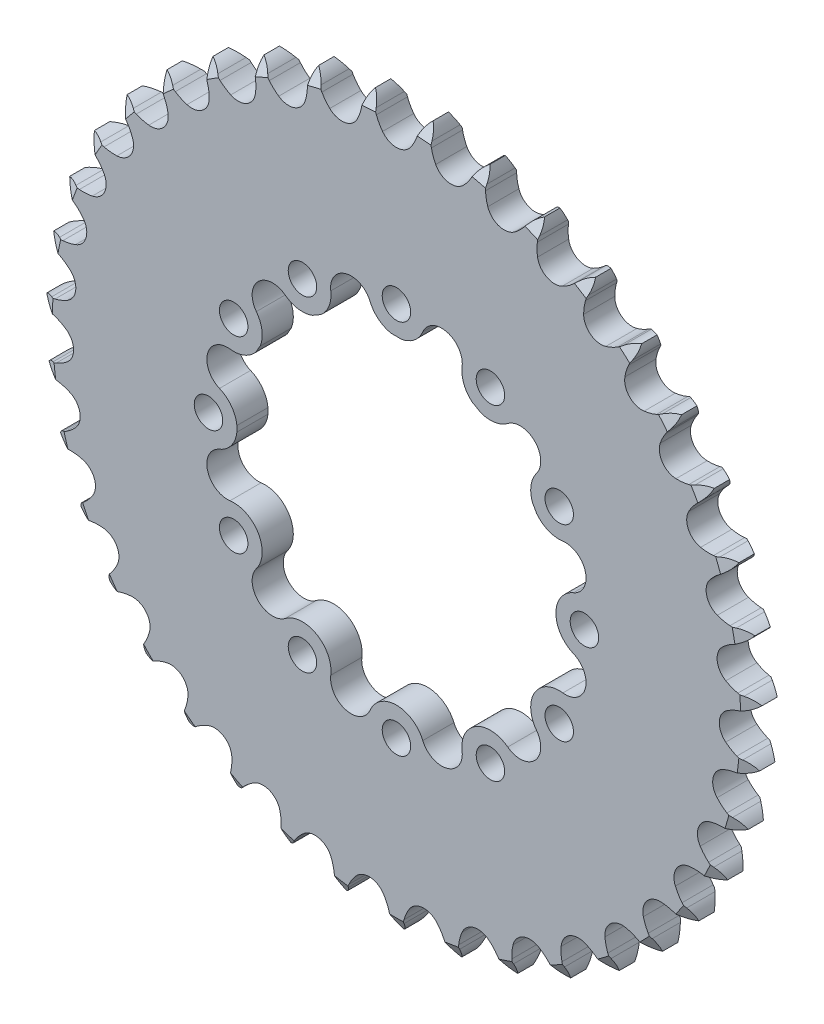
SolidWorks part; units mm, degrees
material "7075-T6 (SN)"
ref_plane "Front Plane" through (0, 0, 0) normal (0, 0, 1) x (1, 0, 0)
ref_plane "Top Plane" through (0, 0, 0) normal (0, 1, 0) x (1, 0, 0)
ref_plane "Right Plane" through (0, 0, 0) normal (1, 0, 0) x (0, 0, -1)
sketch "Work Sketch" plane through (0, 0, 0) normal (0, 0, 1) x (1, 0, 0)
  line L0 (0, 0) -> (0, 160.4542) construction
  line L1 (-112.0919, 78.9148) -> (87.2579, 78.9148) construction
  line L2 (5.102, 120.8822) -> (5.102, 112.9699) construction
  line L3 (-12.8497, 82.6953) -> (16.7256, 82.6953) construction
  line L4 (5.102, 82.6953) -> (-6.0879, 74.4036) construction
  line L5 (5.102, 82.6953) -> (-4.6505, 79.1506) construction
  line L6 (-4.6505, 79.1506) -> (-6.8863, 85.3019)
  line L7 (-11.5114, 78.0206) -> (-7.1525, 78.0206) construction
  line L8 (-11.0765, 124.7602) -> (-11.0765, 110.2345) construction
  line L9 (0, 0) -> (-3.4402, 42.6146) construction
  circle A0 centre (0, 0) radius 78.9148
  circle A1 centre (0, 78.9148) radius 4.0088
  arc A2 (-4.6505, 79.1506) -> (-3.2209, 76.5281) centre (5.0804, 82.7541) ccw
  circle A3 centre (-11.0765, 78.0206) radius 6.4254
  point P23 (-3.2209, 76.5281)
  dimension "D1" = 157.8295
  dimension "D8" = 10.3767
  dimension "D2" = 8.0177
  dimension "D3" = 5.102
  dimension "D4" = 3.7806
  dimension "D5" = 36.538
  dimension "D6" = 16.564
  dimension "D7" = 10.3767
  dimension "D9" = 0.8942
  dimension "D10" = 11.0765
  dimension "D11" = 4.615
sketch "Teeth Sketch" plane through (0, 0, 0) normal (0, 0, 1) x (1, 0, 0)
  line L0 (5.0376, 80.2155) -> (4.6505, 79.1506)
  line L1 (-7.4865, 92.7372) -> (-4.7839, 59.2593) construction
  line L2 (0, 0) -> (-10.9133, 132.3061) construction
  line L3 (7.8951, 79.9848) -> (8.1063, 78.8717)
  line L4 (16093.3137, -199351.4616) -> (-16096.7539, 199394.0762) construction
  line L5 (0, 146.3285) -> (0, 56.9858) construction
  line L6 (17.8398, 78.3686) -> (17.287, 77.3797)
  line L7 (0, -200000) -> (0, 200160.4542) construction
  line L8 (20.6234, 77.6826) -> (20.6533, 76.5499)
  line L9 (-4.6505, 79.1506) -> (-6.8863, 85.3019) construction
  line L10 (44.1616, 67.154) -> (43.8313, 66.0702)
  line L11 (-5.0376, 80.2155) -> (-4.6505, 79.1506)
  line L12 (30.18, 74.4921) -> (29.4757, 73.6046)
  line L13 (32.8175, 73.3684) -> (32.6653, 72.2456)
  line L14 (41.7385, 68.6862) -> (40.901, 67.9232)
  line L15 (52.2161, 61.1014) -> (51.267, 60.4826)
  line L16 (54.362, 59.2003) -> (53.8621, 58.1836)
  line L17 (61.3413, 51.9341) -> (60.3052, 51.4756)
  line L18 (63.1544, 49.7134) -> (62.4979, 48.79)
  line L19 (68.8777, 41.4218) -> (67.7815, 41.1354)
  line L20 (70.3112, 38.939) -> (69.515, 38.1328)
  line L21 (74.6303, 29.8366) -> (73.5023, 29.7298)
  line L22 (75.6469, 27.156) -> (74.7318, 26.488)
  line L23 (78.45, 17.4787) -> (77.3195, 17.5542)
  line L24 (79.0234, 14.6698) -> (78.013, 14.1572)
  line L25 (80.2378, 4.6681) -> (79.1341, 4.9239)
  line L26 (80.3533, 1.8035) -> (79.2737, 1.4597)
  line L27 (79.9476, -8.2634) -> (78.8992, -7.8338)
  line L28 (79.602, -11.1094) -> (78.4813, -11.2756)
  line L29 (77.5867, -20.9809) -> (76.6208, -20.3887)
  line L30 (76.7891, -23.7346) -> (75.6562, -23.7189)
  line L31 (73.2164, -33.155) -> (72.358, -32.4155)
  line L32 (71.9874, -35.7451) -> (70.8717, -35.5478)
  line L33 (66.9499, -44.4704) -> (66.2212, -43.6028)
  line L34 (65.3213, -46.8298) -> (64.2517, -46.4561)
  line L35 (58.9493, -54.634) -> (58.3693, -53.6608)
  line L36 (56.9634, -56.7016) -> (55.9676, -56.1612)
  line L37 (49.422, -63.3827) -> (49.0056, -62.329)
  line L38 (47.1301, -65.1049) -> (46.2339, -64.4118)
  line L39 (38.6147, -70.4897) -> (38.3727, -69.3829)
  line L40 (36.0763, -71.822) -> (35.3028, -70.9941)
  line L41 (26.8073, -75.7712) -> (26.746, -74.6398)
  line L42 (24.088, -76.679) -> (23.4574, -75.7377)
  line L43 (14.3056, -79.0901) -> (14.4266, -77.9636)
  line L44 (11.4759, -79.55) -> (11.0044, -78.5198)
  line L45 (1.4334, -80.3607) -> (1.7335, -79.2682)
  line L46 (-1.4334, -80.3607) -> (-1.7335, -79.2682)
  line L47 (-11.4759, -79.55) -> (-11.0044, -78.5198)
  line L48 (-14.3056, -79.0901) -> (-14.4266, -77.9636)
  line L49 (-24.088, -76.679) -> (-23.4574, -75.7377)
  line L50 (-26.8073, -75.7712) -> (-26.746, -74.6398)
  line L51 (-36.0763, -71.822) -> (-35.3028, -70.9941)
  line L52 (-38.6147, -70.4897) -> (-38.3727, -69.3829)
  line L53 (-47.1301, -65.1049) -> (-46.2339, -64.4118)
  line L54 (-49.422, -63.3827) -> (-49.0056, -62.329)
  line L55 (-56.9634, -56.7016) -> (-55.9676, -56.1612)
  line L56 (-58.9493, -54.634) -> (-58.3693, -53.6608)
  line L57 (-65.3213, -46.8298) -> (-64.2517, -46.4561)
  line L58 (-66.9499, -44.4704) -> (-66.2212, -43.6028)
  line L59 (-71.9874, -35.7451) -> (-70.8717, -35.5478)
  line L60 (-73.2164, -33.155) -> (-72.358, -32.4155)
  line L61 (-76.7891, -23.7346) -> (-75.6562, -23.7189)
  line L62 (-77.5867, -20.9809) -> (-76.6208, -20.3887)
  line L63 (-79.602, -11.1094) -> (-78.4813, -11.2756)
  line L64 (-79.9476, -8.2634) -> (-78.8992, -7.8338)
  line L65 (-80.3533, 1.8035) -> (-79.2737, 1.4597)
  line L66 (-80.2378, 4.6681) -> (-79.1341, 4.9239)
  line L67 (-79.0234, 14.6698) -> (-78.013, 14.1572)
  line L68 (-78.45, 17.4787) -> (-77.3195, 17.5542)
  line L69 (-75.6469, 27.156) -> (-74.7318, 26.488)
  line L70 (-74.6303, 29.8366) -> (-73.5023, 29.7298)
  line L71 (-70.3112, 38.939) -> (-69.515, 38.1328)
  line L72 (-68.8777, 41.4218) -> (-67.7815, 41.1354)
  line L73 (-63.1544, 49.7134) -> (-62.4979, 48.79)
  line L74 (-61.3413, 51.9341) -> (-60.3052, 51.4756)
  line L75 (-54.362, 59.2003) -> (-53.8621, 58.1836)
  line L76 (-52.2161, 61.1014) -> (-51.267, 60.4826)
  line L77 (-44.1616, 67.154) -> (-43.8313, 66.0702)
  line L78 (-41.7385, 68.6862) -> (-40.901, 67.9232)
  line L79 (-32.8175, 73.3684) -> (-32.6653, 72.2456)
  line L80 (-30.18, 74.4921) -> (-29.4757, 73.6046)
  line L81 (-20.6234, 77.6826) -> (-20.6533, 76.5499)
  line L82 (-17.8398, 78.3686) -> (-17.287, 77.3797)
  line L83 (-7.8951, 79.9848) -> (-8.1063, 78.8717)
  arc A0 (-6.8336, 82.8459) -> (-5.0376, 80.2155) centre (-11.0765, 78.0206) cw
  circle A1 centre (-11.0765, 78.0206) radius 6.4254 construction
  arc A2 (-3.2209, 76.5281) -> (-4.6505, 79.1506) centre (5.0804, 82.7541) cw
  arc A3 (-4.6505, 79.1506) -> (-3.2209, 76.5281) centre (5.0804, 82.7541) ccw construction
  circle A4 centre (0, 78.9148) radius 4.0088 construction
  arc A5 (-3.2209, 76.5281) -> (3.2209, 76.5281) centre (0, 78.9148) ccw
  arc A6 (3.2209, 76.5281) -> (4.6505, 79.1506) centre (-5.0804, 82.7541) ccw
  arc A7 (6.8336, 82.8459) -> (5.0376, 80.2155) centre (11.0765, 78.0206) ccw
  arc A8 (6.5443, 82.8692) -> (7.8951, 79.9848) centre (1.5824, 78.787) cw
  arc A9 (9.0967, 76.0537) -> (8.1063, 78.8717) centre (18.2893, 80.8676) cw
  arc A10 (9.0967, 76.0537) -> (15.4552, 75.0204) centre (12.6588, 77.8928) ccw
  arc A11 (15.4552, 75.0204) -> (17.287, 77.3797) centre (8.2601, 82.4975) ccw
  arc A12 (20.0345, 80.6769) -> (17.8398, 78.3686) centre (23.4484, 75.2334) ccw
  arc A13 (19.7528, 80.7463) -> (20.6234, 77.6826) centre (14.2002, 77.5129) cw
  arc A14 (21.1788, 73.6096) -> (20.6533, 76.5499) centre (31.0245, 76.8865) cw
  arc A15 (21.1788, 73.6096) -> (27.2892, 71.5697) centre (24.9898, 74.8535) ccw
  arc A16 (27.2892, 71.5697) -> (29.4757, 73.6046) centre (21.3867, 80.1041) ccw
  arc A17 (32.7165, 76.4184) -> (30.18, 74.4921) centre (35.2131, 70.4978) ccw
  arc A18 (32.4496, 76.5321) -> (32.8175, 73.3684) centre (26.4502, 74.2313) cw
  arc A19 (32.7124, 69.2591) -> (32.6653, 72.2456) centre (42.9562, 70.9142) cw
  arc A20 (32.7124, 69.2591) -> (38.4163, 66.2654) centre (36.6735, 69.8756) ccw
  arc A21 (38.4163, 66.2654) -> (40.901, 67.9232) centre (33.9593, 75.6361) ccw
  arc A22 (44.5512, 70.1807) -> (41.7385, 68.6862) centre (46.0657, 63.9363) ccw
  arc A23 (44.306, 70.3358) -> (44.1616, 67.154) centre (38.0153, 69.0271) cw
  arc A24 (43.3987, 63.1147) -> (43.8313, 66.0702) centre (53.7754, 63.1052) cw
  arc A25 (43.3987, 63.1147) -> (48.5486, 59.2448) centre (47.4074, 63.0878) ccw
  arc A26 (48.5486, 59.2448) -> (51.267, 60.4826) centre (45.6524, 69.2092) ccw
  arc A27 (55.2321, 62.1253) -> (52.2161, 61.1014) centre (55.7253, 55.7189) ccw
  arc A28 (55.0149, 62.3178) -> (54.362, 59.2003) centre (48.5957, 62.0351) cw
  arc A29 (52.961, 55.3358) -> (53.8621, 58.1836) centre (63.2018, 53.6618) cw
  arc A30 (52.961, 55.3358) -> (57.4234, 50.6899) centre (56.9135, 54.6662) ccw
  arc A31 (57.4234, 50.6899) -> (60.3052, 51.4756) centre (56.1632, 60.9898) ccw
  arc A32 (64.4824, 52.461) -> (61.3413, 51.9341) centre (63.9416, 46.0584) ccw
  arc A33 (64.2989, 52.6858) -> (63.1544, 49.7134) centre (57.9175, 53.4365) cw
  arc A34 (61.1517, 46.1237) -> (62.4979, 48.79) centre (70.9913, 42.8287) cw
  arc A35 (61.1517, 46.1237) -> (64.811, 40.8221) centre (64.9456, 44.8287) ccw
  arc A36 (64.811, 40.8221) -> (67.7815, 41.1354) centre (65.2193, 51.1908) ccw
  arc A37 (72.0627, 41.4379) -> (68.8777, 41.4218) centre (70.5018, 35.205) ccw
  arc A38 (71.9177, 41.6892) -> (70.3112, 38.939) centre (65.7393, 43.4539) cw
  arc A39 (67.7585, 35.717) -> (69.515, 38.1328) centre (76.9422, 30.8862) cw
  arc A40 (67.7585, 35.717) -> (70.5201, 29.8971) centre (71.2956, 33.8302) ccw
  arc A41 (70.5201, 29.8971) -> (73.5023, 29.7298) centre (72.5864, 40.0659) ccw
  arc A42 (77.7767, 29.3416) -> (74.6303, 29.8366) centre (75.2361, 23.4398) ccw
  arc A43 (77.6738, 29.6129) -> (75.6469, 27.156) centre (71.8585, 32.3458) cw
  arc A44 (72.6105, 24.3852) -> (74.7318, 26.488) centre (80.9003, 18.1439) cw
  arc A45 (72.6105, 24.3852) -> (74.4027, 18.1977) centre (75.7991, 21.9555) ccw
  arc A46 (74.4027, 18.1977) -> (77.3195, 17.5542) centre (78.0734, 27.9034) ccw
  arc A47 (81.4762, 16.4854) -> (78.45, 17.4787) centre (78.0218, 11.0675) ccw
  arc A48 (81.4182, 16.7697) -> (79.0234, 14.6698) centre (76.1166, 20.4) cw
  arc A49 (75.5818, 12.4219) -> (78.013, 14.1572) centre (82.7631, 4.9316) cw
  arc A50 (75.5818, 12.4219) -> (76.3583, 6.027) centre (78.3394, 9.5121) ccw
  arc A51 (76.3583, 6.027) -> (79.1341, 4.9239) centre (81.5384, 15.0182) ccw
  arc A52 (83.0656, 3.2022) -> (80.2378, 4.6681) centre (78.7868, -1.5914) ccw
  arc A53 (83.0539, 3.4922) -> (80.3533, 1.8035) centre (78.4033, 7.9259) cw
  arc A54 (76.5957, 0.1368) -> (79.2737, 1.4597) centre (82.4825, -8.4084) cw
  arc A55 (76.5957, 0.1368) -> (76.3363, -6.2998) centre (78.8508, -3.1776) ccw
  arc A56 (76.3363, -6.2998) -> (78.8992, -7.8338) centre (82.8916, 1.7441) ccw
  arc A57 (82.5035, -10.1639) -> (79.9476, -8.2634) centre (77.5113, -14.2091) ccw
  arc A58 (82.5385, -9.8758) -> (79.602, -11.1094) centre (78.6594, -4.7535) cw
  arc A59 (75.6257, -12.1517) -> (78.4813, -11.2756) centre (80.0655, -21.5307) cw
  arc A60 (75.6257, -12.1517) -> (74.3372, -18.4634) centre (77.3199, -15.785) ccw
  arc A61 (74.3372, -18.4634) -> (76.6208, -20.3887) centre (82.0979, -11.5753) ccw
  arc A62 (79.8047, -23.2668) -> (77.5867, -20.9809) centre (74.2283, -26.4587) ccw
  arc A63 (79.8855, -22.9881) -> (76.7891, -23.7346) centre (76.8783, -17.3098) cw
  arc A64 (72.6971, -24.1256) -> (75.6562, -23.7189) centre (75.5749, -34.0953) cw
  arc A65 (72.6971, -24.1256) -> (70.4128, -30.1488) centre (73.7866, -27.9836) ccw
  arc A66 (70.4128, -30.1488) -> (72.358, -32.4155) centre (79.178, -24.5948) ccw
  arc A67 (75.039, -35.7671) -> (73.2164, -33.155) centre (69.0227, -38.0232) ccw
  arc A68 (75.1634, -35.5049) -> (71.9874, -35.7451) centre (73.106, -29.4178) cw
  arc A69 (67.8857, -35.4746) -> (70.8717, -35.5478) centre (69.127, -45.7768) cw
  arc A70 (67.8857, -35.4746) -> (64.6648, -41.0534) centre (68.3422, -39.4574) ccw
  arc A71 (64.6648, -41.0534) -> (66.2212, -43.6028) centre (74.2074, -36.9773) ccw
  arc A72 (68.3299, -47.341) -> (66.9499, -44.4704) centre (62.0296, -48.6028) ccw
  arc A73 (68.4947, -47.1022) -> (65.3213, -46.8298) centre (67.4404, -40.7639) cw
  arc A74 (61.3161, -45.9049) -> (64.2517, -46.4561) centre (60.8887, -56.2728) cw
  arc A75 (61.3161, -45.9049) -> (57.2419, -50.8948) centre (61.1278, -49.9093) ccw
  arc A76 (57.2419, -50.8948) -> (58.3693, -53.6608) centre (67.3148, -48.4022) ccw
  arc A77 (59.851, -57.6888) -> (58.9493, -54.634) centre (53.4299, -57.9236) ccw
  arc A78 (60.052, -57.4796) -> (56.9634, -56.7016) centre (60.0281, -51.0542) cw
  arc A79 (53.1584, -55.1462) -> (55.9676, -56.1612) centre (51.0734, -65.3113) cw
  arc A80 (53.1584, -55.1462) -> (48.3366, -59.4179) centre (52.3302, -59.0685) ccw
  arc A81 (48.3366, -59.4179) -> (49.0056, -62.329) centre (58.6789, -58.5735) ccw
  arc A82 (49.822, -66.5425) -> (49.422, -63.3827) centre (43.4464, -65.7443) ccw
  arc A83 (50.054, -66.3682) -> (47.1301, -65.1049) centre (51.0611, -60.0222) cw
  arc A84 (43.6239, -62.9593) -> (46.2339, -64.4118) centre (39.9354, -72.6583) cw
  arc A85 (43.6239, -62.9593) -> (38.1793, -66.4022) centre (42.1772, -66.698) ccw
  arc A86 (38.1793, -66.4022) -> (38.3727, -69.3829) centre (48.5231, -67.2277) ccw
  arc A87 (38.5026, -73.6728) -> (38.6147, -70.4897) centre (32.3376, -71.8622) ccw
  arc A88 (38.7596, -73.538) -> (36.0763, -71.822) centre (40.7716, -67.4357) cw
  arc A89 (32.9596, -69.1417) -> (35.3028, -70.9941) centre (27.763, -78.1234) cw
  arc A90 (32.9596, -69.1417) -> (27.0333, -71.6667) centre (30.932, -72.6) ccw
  arc A91 (27.0333, -71.6667) -> (26.746, -74.6398) centre (37.1107, -74.1408) ccw
  arc A92 (26.1861, -78.8951) -> (26.8073, -75.7712) centre (20.3913, -76.1189) ccw
  arc A93 (26.4613, -78.8032) -> (24.088, -76.679) centre (29.4261, -73.1027) cw
  arc A94 (21.4417, -73.5335) -> (23.4574, -75.7377) centre (14.8716, -81.5653) cw
  arc A95 (21.4417, -73.5335) -> (15.187, -75.0751) centre (18.8855, -76.6216) ccw
  arc A96 (15.187, -75.0751) -> (14.4266, -77.9636) centre (24.7371, -79.1336) ccw
  arc A97 (13.1913, -82.0739) -> (14.3056, -79.0901) centre (7.9169, -78.4042) ccw
  arc A98 (13.4777, -82.0274) -> (11.4759, -79.55) centre (17.3186, -76.8763) cw
  arc A99 (9.3684, -76.0207) -> (11.0044, -78.5198) centre (1.595, -82.8946) cw
  arc A100 (9.3684, -76.0207) -> (2.9475, -76.5391) centre (6.35, -78.6589) ccw
  arc A101 (2.9475, -76.5391) -> (1.7335, -79.2682) centre (11.7228, -82.077) ccw
  arc A102 (-0.1451, -83.1271) -> (1.4334, -80.3607) centre (-4.7625, -78.6589) ccw
  arc A103 (0.1451, -83.1271) -> (-1.4334, -80.3607) centre (4.7625, -78.6589) cw
  arc A104 (-2.9475, -76.5391) -> (-1.7335, -79.2682) centre (-11.7228, -82.077) cw
  arc A105 (-2.9475, -76.5391) -> (-9.3684, -76.0207) centre (-6.35, -78.6589) ccw
  arc A106 (-9.3684, -76.0207) -> (-11.0044, -78.5198) centre (-1.595, -82.8946) ccw
  arc A107 (-13.4777, -82.0274) -> (-11.4759, -79.55) centre (-17.3186, -76.8763) ccw
  arc A108 (-13.1913, -82.0739) -> (-14.3056, -79.0901) centre (-7.9169, -78.4042) cw
  arc A109 (-15.187, -75.0751) -> (-14.4266, -77.9636) centre (-24.7371, -79.1336) cw
  arc A110 (-15.187, -75.0751) -> (-21.4417, -73.5335) centre (-18.8855, -76.6216) ccw
  arc A111 (-21.4417, -73.5335) -> (-23.4574, -75.7377) centre (-14.8716, -81.5653) ccw
  arc A112 (-26.4613, -78.8032) -> (-24.088, -76.679) centre (-29.4261, -73.1027) ccw
  arc A113 (-26.1861, -78.8951) -> (-26.8073, -75.7712) centre (-20.3913, -76.1189) cw
  arc A114 (-27.0333, -71.6667) -> (-26.746, -74.6398) centre (-37.1107, -74.1408) cw
  arc A115 (-27.0333, -71.6667) -> (-32.9596, -69.1417) centre (-30.932, -72.6) ccw
  arc A116 (-32.9596, -69.1417) -> (-35.3028, -70.9941) centre (-27.763, -78.1234) ccw
  arc A117 (-38.7596, -73.538) -> (-36.0763, -71.822) centre (-40.7716, -67.4357) ccw
  arc A118 (-38.5026, -73.6728) -> (-38.6147, -70.4897) centre (-32.3376, -71.8622) cw
  arc A119 (-38.1793, -66.4022) -> (-38.3727, -69.3829) centre (-48.5231, -67.2277) cw
  arc A120 (-38.1793, -66.4022) -> (-43.6239, -62.9593) centre (-42.1772, -66.698) ccw
  arc A121 (-43.6239, -62.9593) -> (-46.2339, -64.4118) centre (-39.9354, -72.6583) ccw
  arc A122 (-50.054, -66.3682) -> (-47.1301, -65.1049) centre (-51.0611, -60.0222) ccw
  arc A123 (-49.822, -66.5425) -> (-49.422, -63.3827) centre (-43.4464, -65.7443) cw
  arc A124 (-48.3366, -59.4179) -> (-49.0056, -62.329) centre (-58.6789, -58.5735) cw
  arc A125 (-48.3366, -59.4179) -> (-53.1584, -55.1462) centre (-52.3302, -59.0685) ccw
  arc A126 (-53.1584, -55.1462) -> (-55.9676, -56.1612) centre (-51.0734, -65.3113) ccw
  arc A127 (-60.052, -57.4796) -> (-56.9634, -56.7016) centre (-60.0281, -51.0542) ccw
  arc A128 (-59.851, -57.6888) -> (-58.9493, -54.634) centre (-53.4299, -57.9236) cw
  arc A129 (-57.2419, -50.8948) -> (-58.3693, -53.6608) centre (-67.3148, -48.4022) cw
  arc A130 (-57.2419, -50.8948) -> (-61.3161, -45.9049) centre (-61.1278, -49.9093) ccw
  arc A131 (-61.3161, -45.9049) -> (-64.2517, -46.4561) centre (-60.8887, -56.2728) ccw
  arc A132 (-68.4947, -47.1022) -> (-65.3213, -46.8298) centre (-67.4404, -40.7639) ccw
  arc A133 (-68.3299, -47.341) -> (-66.9499, -44.4704) centre (-62.0296, -48.6028) cw
  arc A134 (-64.6648, -41.0534) -> (-66.2212, -43.6028) centre (-74.2074, -36.9773) cw
  arc A135 (-64.6648, -41.0534) -> (-67.8857, -35.4746) centre (-68.3422, -39.4574) ccw
  arc A136 (-67.8857, -35.4746) -> (-70.8717, -35.5478) centre (-69.127, -45.7768) ccw
  arc A137 (-75.1634, -35.5049) -> (-71.9874, -35.7451) centre (-73.106, -29.4178) ccw
  arc A138 (-75.039, -35.7671) -> (-73.2164, -33.155) centre (-69.0227, -38.0232) cw
  arc A139 (-70.4128, -30.1488) -> (-72.358, -32.4155) centre (-79.178, -24.5948) cw
  arc A140 (-70.4128, -30.1488) -> (-72.6971, -24.1256) centre (-73.7866, -27.9836) ccw
  arc A141 (-72.6971, -24.1256) -> (-75.6562, -23.7189) centre (-75.5749, -34.0953) ccw
  arc A142 (-79.8855, -22.9881) -> (-76.7891, -23.7346) centre (-76.8783, -17.3098) ccw
  arc A143 (-79.8047, -23.2668) -> (-77.5867, -20.9809) centre (-74.2283, -26.4587) cw
  arc A144 (-74.3372, -18.4634) -> (-76.6208, -20.3887) centre (-82.0979, -11.5753) cw
  arc A145 (-74.3372, -18.4634) -> (-75.6257, -12.1517) centre (-77.3199, -15.785) ccw
  arc A146 (-75.6257, -12.1517) -> (-78.4813, -11.2756) centre (-80.0655, -21.5307) ccw
  arc A147 (-82.5385, -9.8758) -> (-79.602, -11.1094) centre (-78.6594, -4.7535) ccw
  arc A148 (-82.5035, -10.1639) -> (-79.9476, -8.2634) centre (-77.5113, -14.2091) cw
  arc A149 (-76.3363, -6.2998) -> (-78.8992, -7.8338) centre (-82.8916, 1.7441) cw
  arc A150 (-76.3363, -6.2998) -> (-76.5957, 0.1368) centre (-78.8508, -3.1776) ccw
  arc A151 (-76.5957, 0.1368) -> (-79.2737, 1.4597) centre (-82.4825, -8.4084) ccw
  arc A152 (-83.0539, 3.4922) -> (-80.3533, 1.8035) centre (-78.4033, 7.9259) ccw
  arc A153 (-83.0656, 3.2022) -> (-80.2378, 4.6681) centre (-78.7868, -1.5914) cw
  arc A154 (-76.3583, 6.027) -> (-79.1341, 4.9239) centre (-81.5384, 15.0182) cw
  arc A155 (-76.3583, 6.027) -> (-75.5818, 12.4219) centre (-78.3394, 9.5121) ccw
  arc A156 (-75.5818, 12.4219) -> (-78.013, 14.1572) centre (-82.7631, 4.9316) ccw
  arc A157 (-81.4182, 16.7697) -> (-79.0234, 14.6698) centre (-76.1166, 20.4) ccw
  arc A158 (-81.4762, 16.4854) -> (-78.45, 17.4787) centre (-78.0218, 11.0675) cw
  arc A159 (-74.4027, 18.1977) -> (-77.3195, 17.5542) centre (-78.0734, 27.9034) cw
  arc A160 (-74.4027, 18.1977) -> (-72.6105, 24.3852) centre (-75.7991, 21.9555) ccw
  arc A161 (-72.6105, 24.3852) -> (-74.7318, 26.488) centre (-80.9003, 18.1439) ccw
  arc A162 (-77.6738, 29.6129) -> (-75.6469, 27.156) centre (-71.8585, 32.3458) ccw
  arc A163 (-77.7767, 29.3416) -> (-74.6303, 29.8366) centre (-75.2361, 23.4398) cw
  arc A164 (-70.5201, 29.8971) -> (-73.5023, 29.7298) centre (-72.5864, 40.0659) cw
  arc A165 (-70.5201, 29.8971) -> (-67.7585, 35.717) centre (-71.2956, 33.8302) ccw
  arc A166 (-67.7585, 35.717) -> (-69.515, 38.1328) centre (-76.9422, 30.8862) ccw
  arc A167 (-71.9177, 41.6892) -> (-70.3112, 38.939) centre (-65.7393, 43.4539) ccw
  arc A168 (-72.0627, 41.4379) -> (-68.8777, 41.4218) centre (-70.5018, 35.205) cw
  arc A169 (-64.811, 40.8221) -> (-67.7815, 41.1354) centre (-65.2193, 51.1908) cw
  arc A170 (-64.811, 40.8221) -> (-61.1517, 46.1237) centre (-64.9456, 44.8287) ccw
  arc A171 (-61.1517, 46.1237) -> (-62.4979, 48.79) centre (-70.9913, 42.8287) ccw
  arc A172 (-64.2989, 52.6858) -> (-63.1544, 49.7134) centre (-57.9175, 53.4365) ccw
  arc A173 (-64.4824, 52.461) -> (-61.3413, 51.9341) centre (-63.9416, 46.0584) cw
  arc A174 (-57.4234, 50.6899) -> (-60.3052, 51.4756) centre (-56.1632, 60.9898) cw
  arc A175 (-57.4234, 50.6899) -> (-52.961, 55.3358) centre (-56.9135, 54.6662) ccw
  arc A176 (-52.961, 55.3358) -> (-53.8621, 58.1836) centre (-63.2018, 53.6618) ccw
  arc A177 (-55.0149, 62.3178) -> (-54.362, 59.2003) centre (-48.5957, 62.0351) ccw
  arc A178 (-55.2321, 62.1253) -> (-52.2161, 61.1014) centre (-55.7253, 55.7189) cw
  arc A179 (-48.5486, 59.2448) -> (-51.267, 60.4826) centre (-45.6524, 69.2092) cw
  arc A180 (-48.5486, 59.2448) -> (-43.3987, 63.1147) centre (-47.4074, 63.0878) ccw
  arc A181 (-43.3987, 63.1147) -> (-43.8313, 66.0702) centre (-53.7754, 63.1052) ccw
  arc A182 (-44.306, 70.3358) -> (-44.1616, 67.154) centre (-38.0153, 69.0271) ccw
  arc A183 (-44.5512, 70.1807) -> (-41.7385, 68.6862) centre (-46.0657, 63.9363) cw
  arc A184 (-38.4163, 66.2654) -> (-40.901, 67.9232) centre (-33.9593, 75.6361) cw
  arc A185 (-38.4163, 66.2654) -> (-32.7124, 69.2591) centre (-36.6735, 69.8756) ccw
  arc A186 (-32.7124, 69.2591) -> (-32.6653, 72.2456) centre (-42.9562, 70.9142) ccw
  arc A187 (-32.4496, 76.5321) -> (-32.8175, 73.3684) centre (-26.4502, 74.2313) ccw
  arc A188 (-32.7165, 76.4184) -> (-30.18, 74.4921) centre (-35.2131, 70.4978) cw
  arc A189 (-27.2892, 71.5697) -> (-29.4757, 73.6046) centre (-21.3867, 80.1041) cw
  arc A190 (-27.2892, 71.5697) -> (-21.1788, 73.6096) centre (-24.9898, 74.8535) ccw
  arc A191 (-21.1788, 73.6096) -> (-20.6533, 76.5499) centre (-31.0245, 76.8865) ccw
  arc A192 (-19.7528, 80.7463) -> (-20.6234, 77.6826) centre (-14.2002, 77.5129) ccw
  arc A193 (-20.0345, 80.6769) -> (-17.8398, 78.3686) centre (-23.4484, 75.2334) cw
  arc A194 (-15.4552, 75.0204) -> (-17.287, 77.3797) centre (-8.2601, 82.4975) cw
  arc A195 (-15.4552, 75.0204) -> (-9.0967, 76.0537) centre (-12.6588, 77.8928) ccw
  arc A196 (-9.0967, 76.0537) -> (-8.1063, 78.8717) centre (-18.2893, 80.8676) ccw
  arc A197 (-6.5443, 82.8692) -> (-7.8951, 79.9848) centre (-1.5824, 78.787) ccw
  point P77 (0, 0)
  dimension "D1" = 4.615
  dimension "D2" = 4.715
  dimension "D3" = 39
extrude "Extrusion" add sketch "Teeth Sketch" along normal blind 7.2136
hole_wizard "M6 Clearance Hole1" positions "Sketch6" profile "Sketch7" hole size "M6" standard "ANSI Metric"
sketch "Sketch6" plane through (0, 0, 0) normal (0, 0, -1) x (-1, 0, 0)
  circle A0 centre (0, 0) radius 43.5
  point P0 (0, 43.5)
  dimension "D1" = 87
sketch "Sketch7" plane through (0, 43.5, 0) normal (1, 0, 0) x (0, 1, 0)
  line L0 (0, 0) -> (0, 19.2548)
  line L1 (0, 19.2548) -> (3.3, 17.272)
  line L2 (3.3, 17.272) -> (3.3, 0)
  line L5 (3.3, 0) -> (0, 0)
  line L10 (0, 19.2548) -> (-3.3, 17.272) construction
  line L11 (0, -6.35) -> (0, 107.95) construction
  dimension "Hole Dia." = 6.6
  dimension "Hole Depth" = 17.272
  dimension "Drill Angle" = 118
pattern_circular "CirPattern1" count 12 over 360 about axis through (0, -0.0788, 0) along (0, 0, 1) of "M6 Clearance Hole1"
sketch "Sketch8" plane through (0, 0, 0) normal (0, 0, -1) x (-1, 0, 0)
  circle A0 centre (0, 0) radius 37
  dimension "D1" = 74
extrude "Cut-Extrude1" cut sketch "Sketch8" against normal through all both and the other way through all
ref_plane "Sprocket Center Plane" through (0, 0, 3.6068) normal (0, 0, 1) x (1, 0, 0)
sketch "Pitch Circle" plane through (0, 0, 3.6068) normal (0, 0, -1) x (-1, 0, 0)
  circle A0 centre (0, 0) radius 78.9148 construction
  dimension "D1" = 157.8295
ref_plane "Center Plane" through (0, 0, 3.6068) normal (0, 0, 1) x (1, 0, 0)
ref_axis "Axis1" through (0, 0, 7.2136) along (0, 0, -1)
sketch "Sketch5" plane through (0, 0, 0) normal (1, 0, 0) x (0, 0, -1)
  line L0 (-1.8288, -82.9722) -> (-5.3848, -82.9722)
  line L1 (-7.2136, -81.8977) -> (0, -81.8977) construction
  line L2 (-5.3848, -82.9722) -> (-5.3848, -79.7786)
  line L3 (-5.3848, -79.7786) -> (-7.2136, -79.7786)
  line L4 (-7.2136, -79.7786) -> (-5.3848, -82.9722)
  line L5 (-7.2136, -79.7786) -> (-7.2136, -82.9722)
  line L6 (-7.2136, -82.9722) -> (-5.3848, -82.9722)
  line L7 (-7.2136, -82.9722) -> (0, -82.9722) construction
  line L8 (-7.2136, -82.9722) -> (0, -82.9722)
  point P5 (-3.6068, -82.9722)
  point P20 (-3.6068, -82.9722)
  dimension "D1" = 3.556
  dimension "D2" = 3.1936
  dimension "D3" = 1.8288
revolve "Cut-Revolve1" cut sketch "Sketch5" angle 360 about axis through (0, 0, 7.2136) along (0, 0, -1)
mirror "Mirror1" about plane through (0, 0, 3.6068) normal (0, 0, 1) of "Cut-Revolve1"
sketch "Sketch9" plane through (0, 0, 7.2136) normal (0, 0, 1) x (1, 0, 0)
  line L0 (0, -43.6576) -> (0, -74.9059) construction
  line L1 (0, -43.6576) -> (21.7894, -37.8192) construction
  line L2 (10.8947, -40.7384) -> (19.3521, -72.3629) construction
  line L3 (21.7894, -37.8192) -> (37.3944, -64.9042) construction
  line L28 (24.0494, -61.143) -> (24.0619, -47.3154)
  line L29 (28.865, -44.5481) -> (40.8338, -51.4727)
  line L30 (-9.7441, -64.9761) -> (-2.8195, -53.0073)
  line L31 (2.7238, -53.0123) -> (9.6267, -64.9936)
  line L32 (-40.9267, -51.3989) -> (-28.9454, -44.4959)
  line L33 (-24.1473, -47.2719) -> (-24.1598, -61.0994)
  line L34 (-61.143, -24.0494) -> (-47.3154, -24.0619)
  line L35 (-44.5481, -28.865) -> (-51.4727, -40.8338)
  line L36 (-64.9761, 9.7441) -> (-53.0073, 2.8195)
  line L37 (-53.0123, -2.7238) -> (-64.9936, -9.6267)
  line L38 (-51.3989, 40.9267) -> (-44.4959, 28.9454)
  line L39 (-47.2719, 24.1473) -> (-61.0994, 24.1598)
  line L40 (-24.0494, 61.143) -> (-24.0619, 47.3154)
  line L41 (-28.865, 44.5481) -> (-40.8338, 51.4727)
  line L42 (9.7441, 64.9761) -> (2.8195, 53.0073)
  line L43 (-2.7238, 53.0123) -> (-9.6267, 64.9936)
  line L44 (40.9267, 51.3989) -> (28.9454, 44.4959)
  line L45 (24.1473, 47.2719) -> (24.1598, 61.0994)
  line L46 (61.143, 24.0494) -> (47.3154, 24.0619)
  line L47 (44.5481, 28.865) -> (51.4727, 40.8338)
  line L48 (64.9761, -9.7441) -> (53.0073, -2.8195)
  line L49 (53.0123, 2.7238) -> (64.9936, 9.6267)
  line L50 (51.3989, -40.9267) -> (44.4959, -28.9454)
  line L51 (47.2719, -24.1473) -> (61.0994, -24.1598)
  line L52 (20.0159, -62.8794) -> (20.0223, -49.6148)
  line L53 (15.9951, -46.5215) -> (9.3619, -48.2954)
  line L54 (7.4163, -52.986) -> (14.0431, -64.4767)
  circle A0 centre (0, 43.5) radius 6.6183
  circle A1 centre (21.7894, 37.6615) radius 6.6183
  circle A2 centre (37.7404, 21.7106) radius 6.6183
  circle A3 centre (43.5788, -0.0788) radius 6.6183
  circle A4 centre (37.7404, -21.8682) radius 6.6183
  circle A5 centre (21.7894, -37.8192) radius 6.6183
  circle A6 centre (0, -43.6576) radius 6.6183
  circle A7 centre (-21.7894, -37.8192) radius 6.6183
  circle A8 centre (-37.7404, -21.8682) radius 6.6183
  circle A9 centre (-43.5788, -0.0788) radius 6.6183
  circle A10 centre (-37.7404, 21.7106) radius 6.6183
  circle A11 centre (-21.7894, 37.6615) radius 6.6183
  circle A12 centre (0, 0) radius 37 construction
  arc A13 (32.014, -18.5501) -> (31.5935, 19.2575) centre (0, 0) ccw
  circle A14 centre (0, 0) radius 74.9059 construction
  arc A15 (9.3684, -76.0207) -> (2.9475, -76.5391) centre (6.35, -78.6589) ccw construction
  arc A21 (-38.585, 15.1464) -> (-41.0283, 6.0283) centre (-39.1929, 10.4229) ccw
  arc A22 (-25.803, 32.3992) -> (-32.478, 25.7242) centre (-28.6912, 28.6124) ccw
  arc A23 (-6.1071, 40.9494) -> (-15.2253, 38.5062) centre (-10.5017, 39.1141) ccw
  arc A24 (15.2253, 38.5062) -> (6.1071, 40.9494) centre (10.5017, 39.1141) ccw
  arc A25 (32.478, 25.7242) -> (25.803, 32.3992) centre (28.6912, 28.6124) ccw
  arc A26 (41.0283, 6.0283) -> (38.585, 15.1464) centre (39.1929, 10.4229) ccw
  arc A27 (38.585, -15.3041) -> (41.0283, -6.1859) centre (39.1929, -10.5805) ccw
  arc A28 (25.803, -32.5568) -> (32.478, -25.8818) centre (28.6912, -28.77) ccw
  arc A29 (-36.9952, 0.5974) -> (-36.9928, -0.7312) centre (0, 0) ccw
  arc A30 (-31.5935, 19.2575) -> (-32.5297, 17.6301) centre (0, 0) ccw
  arc A31 (19.4699, 31.463) -> (-19.4699, 31.463) centre (0, 0) ccw
  arc A33 (6.1071, -41.1071) -> (15.2253, -38.6639) centre (10.5017, -39.2717) ccw
  arc A34 (-15.2253, -38.6639) -> (-6.1071, -41.1071) centre (-10.5017, -39.2717) ccw
  arc A35 (-32.478, -25.8818) -> (-25.803, -32.5568) centre (-28.6912, -28.77) ccw
  arc A36 (-41.0283, -6.1859) -> (-38.585, -15.3041) centre (-39.1929, -10.5805) ccw
  arc A87 (28.5526, -64.0691) -> (41.1066, -56.8361) centre (0, 0) ccw
  arc A88 (41.1066, -56.8361) -> (40.8338, -51.4727) centre (39.2311, -54.2429) ccw
  arc A89 (24.0494, -61.143) -> (28.5526, -64.0691) centre (27.2498, -61.1459) ccw
  arc A90 (28.865, -44.5481) -> (24.0619, -47.3154) centre (27.2623, -47.3183) ccw
  circle A91 centre (0, 0) radius 54.61 construction
  arc A92 (2.7238, -53.0123) -> (-2.8195, -53.0073) centre (-0.0493, -54.61) ccw
  arc A93 (7.1813, -69.7748) -> (9.6267, -64.9936) centre (6.8537, -66.5913) ccw
  arc A94 (-7.3073, -69.7618) -> (7.1813, -69.7748) centre (0, 0) ccw
  arc A95 (-9.7441, -64.9761) -> (-7.3073, -69.7618) centre (-6.9739, -66.5788) ccw
  arc A96 (-24.1473, -47.2719) -> (-28.9454, -44.4959) centre (-27.3477, -47.269) ccw
  arc A97 (-28.6682, -64.0175) -> (-24.1598, -61.0994) centre (-27.3602, -61.0966) ccw
  arc A98 (-41.2092, -56.7618) -> (-28.6682, -64.0175) centre (0, 0) ccw
  arc A99 (-40.9267, -51.3989) -> (-41.2092, -56.7618) centre (-39.329, -54.172) ccw
  arc A100 (-44.5481, -28.865) -> (-47.3154, -24.0619) centre (-47.3183, -27.2623) ccw
  arc A101 (-56.8361, -41.1066) -> (-51.4727, -40.8338) centre (-54.2429, -39.2311) ccw
  arc A102 (-64.0691, -28.5526) -> (-56.8361, -41.1066) centre (0, 0) ccw
  arc A103 (-61.143, -24.0494) -> (-64.0691, -28.5526) centre (-61.1459, -27.2498) ccw
  arc A104 (-53.0123, -2.7238) -> (-53.0073, 2.8195) centre (-54.61, 0.0493) ccw
  arc A105 (-69.7748, -7.1813) -> (-64.9936, -9.6267) centre (-66.5913, -6.8537) ccw
  arc A106 (-69.7618, 7.3073) -> (-69.7748, -7.1813) centre (0, 0) ccw
  arc A107 (-64.9761, 9.7441) -> (-69.7618, 7.3073) centre (-66.5788, 6.9739) ccw
  arc A108 (-47.2719, 24.1473) -> (-44.4959, 28.9454) centre (-47.269, 27.3477) ccw
  arc A109 (-64.0175, 28.6682) -> (-61.0994, 24.1598) centre (-61.0966, 27.3602) ccw
  arc A110 (-56.7618, 41.2092) -> (-64.0175, 28.6682) centre (0, 0) ccw
  arc A111 (-51.3989, 40.9267) -> (-56.7618, 41.2092) centre (-54.172, 39.329) ccw
  arc A112 (-28.865, 44.5481) -> (-24.0619, 47.3154) centre (-27.2623, 47.3183) ccw
  arc A113 (-41.1066, 56.8361) -> (-40.8338, 51.4727) centre (-39.2311, 54.2429) ccw
  arc A114 (-28.5526, 64.0691) -> (-41.1066, 56.8361) centre (0, 0) ccw
  arc A115 (-24.0494, 61.143) -> (-28.5526, 64.0691) centre (-27.2498, 61.1459) ccw
  arc A116 (-2.7238, 53.0123) -> (2.8195, 53.0073) centre (0.0493, 54.61) ccw
  arc A117 (-7.1813, 69.7748) -> (-9.6267, 64.9936) centre (-6.8537, 66.5913) ccw
  arc A118 (7.3073, 69.7618) -> (-7.1813, 69.7748) centre (0, 0) ccw
  arc A119 (9.7441, 64.9761) -> (7.3073, 69.7618) centre (6.9739, 66.5788) ccw
  arc A120 (24.1473, 47.2719) -> (28.9454, 44.4959) centre (27.3477, 47.269) ccw
  arc A121 (28.6682, 64.0175) -> (24.1598, 61.0994) centre (27.3602, 61.0966) ccw
  arc A122 (41.2092, 56.7618) -> (28.6682, 64.0175) centre (0, 0) ccw
  arc A123 (40.9267, 51.3989) -> (41.2092, 56.7618) centre (39.329, 54.172) ccw
  arc A124 (44.5481, 28.865) -> (47.3154, 24.0619) centre (47.3183, 27.2623) ccw
  arc A125 (56.8361, 41.1066) -> (51.4727, 40.8338) centre (54.2429, 39.2311) ccw
  arc A126 (64.0691, 28.5526) -> (56.8361, 41.1066) centre (0, 0) ccw
  arc A127 (61.143, 24.0494) -> (64.0691, 28.5526) centre (61.1459, 27.2498) ccw
  arc A128 (53.0123, 2.7238) -> (53.0073, -2.8195) centre (54.61, -0.0493) ccw
  arc A129 (69.7748, 7.1813) -> (64.9936, 9.6267) centre (66.5913, 6.8537) ccw
  arc A130 (69.7618, -7.3073) -> (69.7748, 7.1813) centre (0, 0) ccw
  arc A131 (64.9761, -9.7441) -> (69.7618, -7.3073) centre (66.5788, -6.9739) ccw
  arc A132 (47.2719, -24.1473) -> (44.4959, -28.9454) centre (47.269, -27.3477) ccw
  arc A133 (64.0175, -28.6682) -> (61.0994, -24.1598) centre (61.0966, -27.3602) ccw
  arc A134 (56.7618, -41.2092) -> (64.0175, -28.6682) centre (0, 0) ccw
  arc A135 (51.3989, -40.9267) -> (56.7618, -41.2092) centre (54.172, -39.329) ccw
  arc A136 (20.0159, -62.8794) -> (14.0431, -64.4767) centre (16.8155, -62.8778) cw
  arc A137 (7.4163, -52.986) -> (9.3619, -48.2954) centre (10.1887, -51.3872) cw
  arc A138 (15.9951, -46.5215) -> (20.0223, -49.6148) centre (16.8219, -49.6132) cw
  circle A139 centre (0, 0) radius 52.3875 construction
  circle A140 centre (0, 0) radius 65.0875 construction
  dimension "D2" = 4.7625
  dimension "D3" = 3.2004
  dimension "D4" = 30
  dimension "D6" = 130.175
  dimension "D10" = 109.22
  dimension "D11" = 4.7625
  dimension "D5" = 104.775
  dimension "D9" = 60
  dimension "D12" = 12
extrude "Center Cutout" cut sketch "Sketch9" against normal through all both and the other way through all contours A9 A36 A8 A35 A7 A34 A6 A33 A5 A28 A4 A13 A3 A2 A25 A1 A31 A0 A11 A22 A10 A21 | A4 A27 A3 A13 | A3 A26 A2 A13 | A31 A0 A23 A11 | A31 A1 A24 A0
equation "\"P\"= 0.500'//Chain Pitch"
equation "\"N\"= 39'//Number of Teeth"
equation "\"Dr\"= 5 / 16'//Roller Diameter"
equation "\"Ds\"= 1.0005 * \"Dr\" + 0.003'Seating Curve DIameter"
equation "\"R\"= \"Ds\" / 2"
equation "\"A\"= 35 + 60 / \"N\""
equation "\"B\"= 18 - 56 / \"N\""
equation "\"ac\"= 0.8 * \"Dr\""
equation "\"M\"= 0.8 * \"Dr\" * cos ( 35 + 60 / \"N\" )"
equation "\"T\"= 0.8 * \"Dr\" * sin ( 35 + 60 / \"N\" )"
equation "\"E\"= 1.3025 * \"Dr\" + 0.0015"
equation "\"Chordal Length of Arc xy\"= ( 2.605 * \"Dr\" + 0.003 ) * sin ( 9 - 28 / \"N\" )"
equation "\"yz\"= \"Dr\" * ( 1.4 * sin ( 17 - 64 / \"N\" ) - 0.8 * sin ( 18 - 56 / \"N\" ) )"
equation "\"ab\"= 1.4 * \"Dr\""
equation "\"W\"= 1.4 * \"Dr\" * cos ( 180 / \"N\" )"
equation "\"V\"= 1.4 * \"Dr\" * sin ( 180 / \"N\" )"
equation "\"F\"= \"Dr\" * ( 0.8 * cos ( 18 - 56 / \"N\" ) + 1.4 * cos ( 17 - 64 / \"N\" ) - 1.3025 )"
equation "\"H\"= sqr ( \"F\" ^ 2 - ( 1.4 * \"Dr\" - \"P\" / 2 ) ^ 2 )"
equation "\"S\"= \"P\" / 2 * cos ( 180 / \"N\" ) + \"H\" * sin ( 180 / \"N\" )"
equation "\"PD\"= \"P\" / ( sin ( 180 / \"N\" ) )"
equation "\"D1@Work Sketch\" = \"PD\""
equation "\"D3@Work Sketch\" = \"M\""
equation "\"D4@Work Sketch\" = \"T\""
equation "\"D5@Work Sketch\" = \"A\""
equation "\"D6@Work Sketch\" = \"B\""
equation "\"D7@Work Sketch\" = \"E\""
equation "\"D8@Work Sketch\" = \"E\""
equation "\"D9@Work Sketch\" = \"V\""
equation "\"D10@Work Sketch\" = \"W\""
equation "\"D2@Work Sketch\" = \"R\" * 2"
equation "\"D11@Work Sketch\" = 180 / \"N\""
equation "\"D2@Teeth Sketch\" = 180 / \"N\" + 0.1"
equation "\"D3@Teeth Sketch\" = \"N\""
equation "\"Edge Thickness\"=0.5"
equation "\"D1@Pitch Circle\"=\"PD\""
equation "\"ST\"= 0.284'//Sprocket Thickness"
